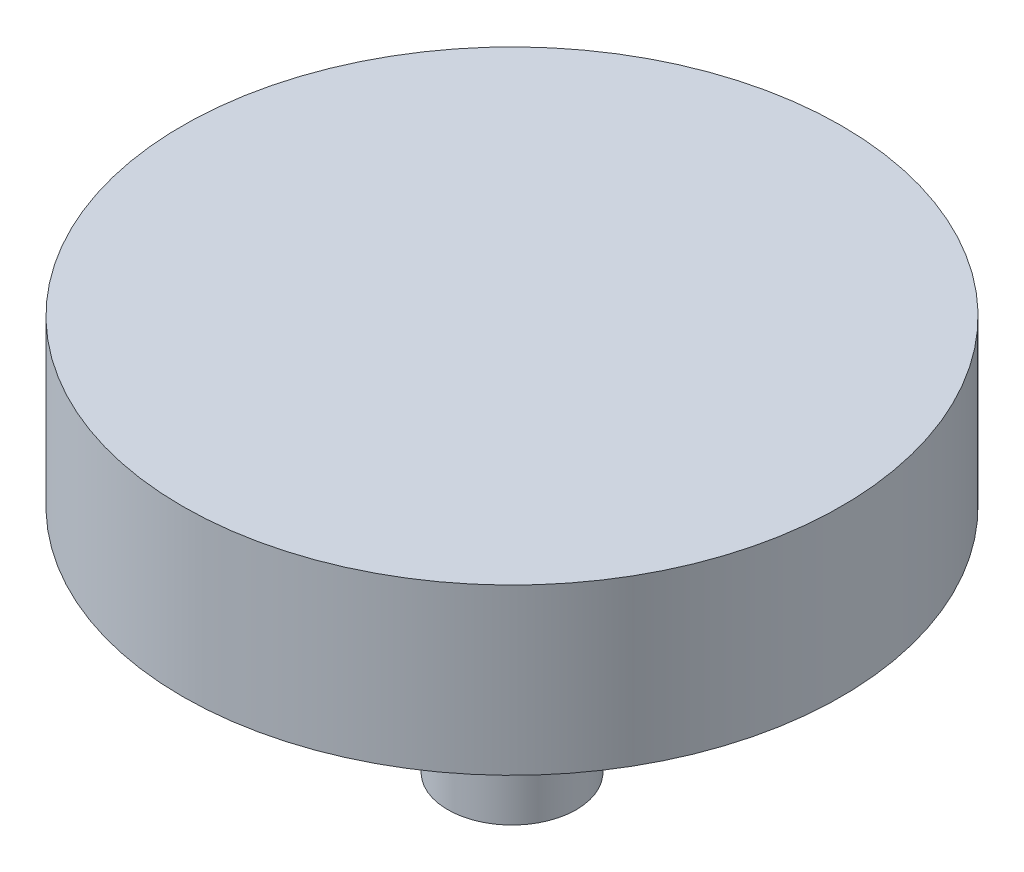
SolidWorks part; units mm, degrees
ref_plane "Front Plane" through (0, 0, 0) normal (0, 0, 1) x (1, 0, 0)
ref_plane "Top Plane" through (0, 0, 0) normal (0, 1, 0) x (1, 0, 0)
ref_plane "Right Plane" through (0, 0, 0) normal (1, 0, 0) x (0, 0, -1)
sketch "Sketch1" plane through (-645.7191, 0, 411.176) normal (0, -1, 0) x (-0.423, 0, 0.9061)
  circle A0 centre (52.9877, -483.5449) radius 10
extrude "Boss-Extrude1" add sketch "Sketch1" along normal blind 5
sketch "Sketch2" plane through (0, -5, 0) normal (0, -1, 0) x (-0.423, 0, 0.9061)
  circle A0 centre (698.7068, -72.369) radius 1.95
extrude "Boss-Extrude2" add sketch "Sketch2" along normal blind 7 contours A0
